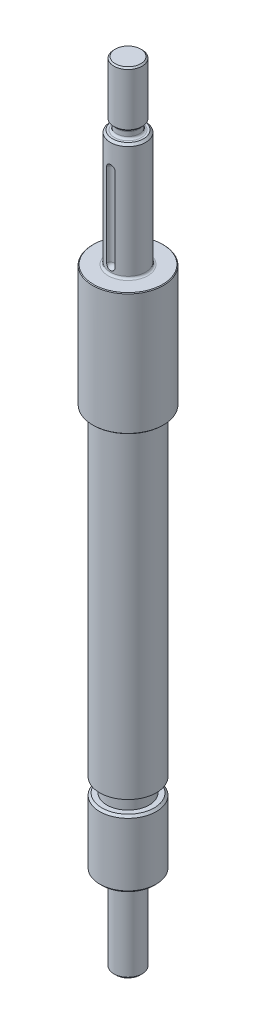
SolidWorks part; units mm, degrees
ref_plane "Front Plane" through (0, 0, 0) normal (0, 0, 1) x (1, 0, 0)
ref_plane "Top Plane" through (0, 0, 0) normal (0, 1, 0) x (1, 0, 0)
ref_plane "Right Plane" through (0, 0, 0) normal (1, 0, 0) x (0, 0, -1)
sketch "Sketch1" plane through (0, 0, 0) normal (0, 0, 1) x (1, 0, 0)
  line L0 (0, 0) -> (0, 119.1505) construction
  line L1 (0, 0) -> (2, 0)
  line L2 (2, 0) -> (2, 12)
  line L3 (2, 12) -> (4, 12)
  line L4 (4, 12) -> (4, 21.5)
  line L5 (4, 69) -> (5, 69)
  line L7 (5, 86.3) -> (2.5, 86.3)
  line L8 (2.5, 86.3) -> (2.5, 102.8)
  line L9 (2, 111.8) -> (0, 111.8)
  line L10 (2, 111.8) -> (2, 104)
  line L11 (1.6, 102.8) -> (2.5, 102.8)
  line L12 (0, 111.8) -> (0, 0)
  line L13 (5, 86.3) -> (5, 69)
  line L15 (2, 104) -> (1.6, 104)
  line L16 (1.6, 104) -> (1.6, 102.8)
  line L17 (4, 23.5) -> (4, 69)
  line L18 (4, 21.5) -> (3, 21.5)
  line L20 (4, 23.5) -> (3, 23.5)
  line L21 (3, 21.5) -> (3, 23.5)
  line L22 (0, 0) -> (0, -13.7807) construction
  dimension "D1" = 17.3
  dimension "D2" = 8
  dimension "D3" = 5
  dimension "D4" = 4
  dimension "D5" = 3.2
  dimension "D6" = 16.5
  dimension "D7" = 10
  dimension "D8" = 1.2
  dimension "D9" = 9
  dimension "D10" = 45.5
  dimension "D11" = 12
  dimension "D12" = 6
  dimension "D13" = 2
  dimension "D14" = 11.5
revolve "Revolve1" add sketch "Sketch1" angle 360 about L0
ref_plane "Plane2" through (0, 86.8, 0) normal (0, 1, 0) x (1, 0, 0)
sketch "Sketch2" plane through (0, 86.8, 0) normal (0, 1, 0) x (1, 0, 0)
  line L0 (0, 0) -> (6.8447, 0) construction
  circle A0 centre (0, 2.5) radius 0.6
  circle A1 centre (0, 0) radius 2.5 construction
  circle A2 centre (0, 0) radius 2.5 construction
  circle A3 centre (0, -2.5) radius 0.6
  dimension "D1" = 1.2
extrude "Cut-Extrude1" cut sketch "Sketch2" along normal offset from surface (13 mm away) 3 up to face at (0, 102.8, -1.6)
fillet "Fillet1" radius 0.6 4 edges at (0, 99.8, -1.9) (0, 86.8, -1.9) (0, 86.8, 1.9) (0, 99.8, 1.9)
chamfer "Chamfer1" distance 0.1 angle 45 2 edges at (0, 69, -5) (0, 86.3, -5)
chamfer "Chamfer2" distance 0.3 angle 45 2 edges at (0, 21.5, -4) (0, 12, -4)
chamfer "Chamfer3" distance 0.3 angle 45 1 edges at (0, 0, -2)
chamfer "Chamfer4" distance 0.3 angle 45 1 edges at (0, 102.8, -2.5)
chamfer "Chamfer5" distance 0.2 angle 45 2 edges at (0, 104, -2) (0, 111.8, -2)
fillet "Fillet2" radius 0.3 6 edges at (0, 23.5, -3) (0, 12, -2) (0, 69, -4) (0, 86.3, -2.5) (0, 104, -1.6) (0, 102.8, -1.6)
